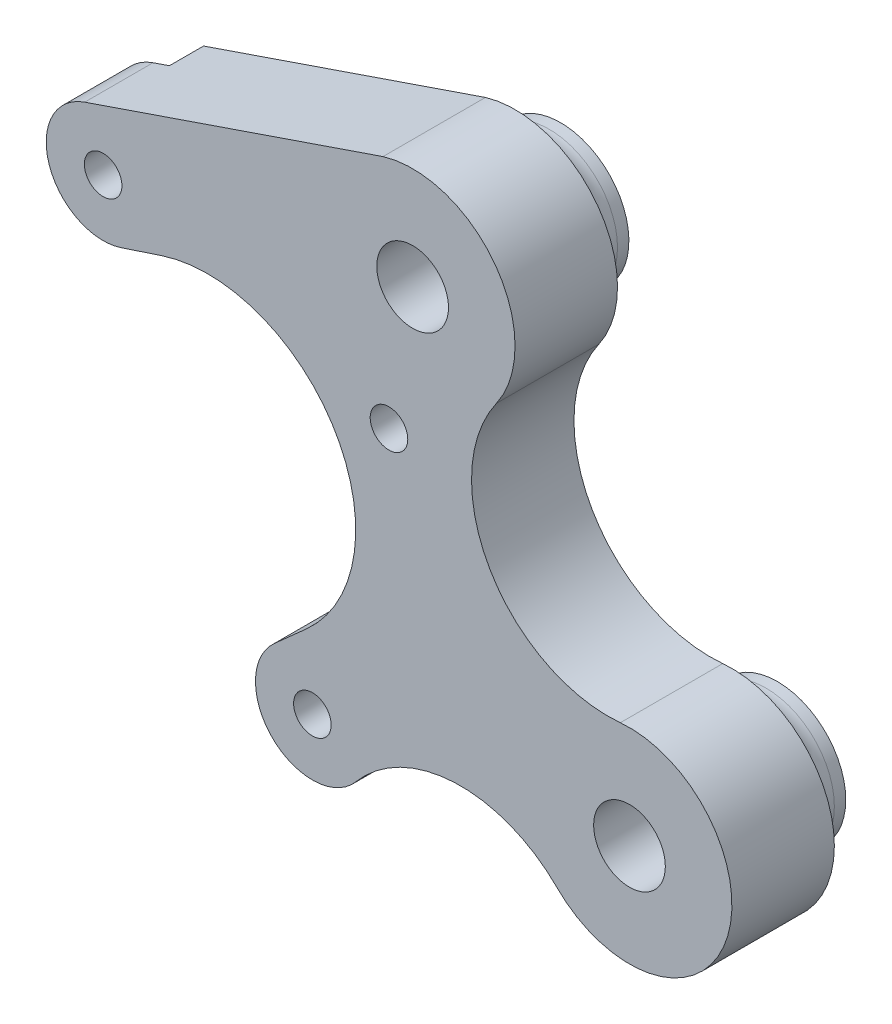
SolidWorks part; units mm, degrees
ref_plane "Front Plane" through (0, 0, 0) normal (0, 0, 1) x (1, 0, 0)
ref_plane "Top Plane" through (0, 0, 0) normal (0, 1, 0) x (1, 0, 0)
ref_plane "Right Plane" through (0, 0, 0) normal (1, 0, 0) x (0, 0, -1)
sketch "Sketch1" plane through (0, 0, 0) normal (0, 0, 1) x (1, 0, 0)
  line L0 (18, 21) -> (37.0525, -11.9999) construction
  line L1 (15.9217, 9.1924) -> (-9.1924, 15.9217) construction
  line L2 (-9.1924, 15.9217) -> (-15.9217, -9.1924) construction
  line L3 (-15.9217, -9.1924) -> (9.1924, -15.9217) construction
  line L4 (9.1924, -15.9217) -> (15.9217, 9.1924) construction
  line L5 (0, 0) -> (50.7667, 0) construction
  line L6 (0, 0) -> (-9.1924, 15.9217) construction
  line L7 (-4.0727, 12.3456) -> (-7.626, 11.1734)
  line L8 (8.6552, -9.6998) -> (5.8634, -12.191)
  line L9 (0, 0) -> (9.1924, -15.9217) construction
  line L10 (15.3981, 29.6157) -> (-10.8103, 20.6527)
  arc A0 (8.6552, -9.6998) -> (-4.0727, 12.3456) centre (0, 0) ccw
  circle A1 centre (18, 21) radius 3.15
  circle A2 centre (-9.1924, 15.9217) radius 1.65
  circle A3 centre (15.9217, 9.1924) radius 1.65
  circle A4 centre (9.1924, -15.9217) radius 1.65
  arc A5 (25.3607, 15.8211) -> (15.3981, 29.6157) centre (18, 21) ccw
  circle A6 centre (37.0525, -11.9999) radius 3.15
  arc A7 (-10.8103, 20.6527) -> (-7.626, 11.1734) centre (-9.1924, 15.9217) ccw
  arc A9 (30.6913, -18.3666) -> (36.2478, -3.0359) centre (37.0525, -11.9999) ccw
  arc A10 (5.8634, -12.191) -> (13.021, -19.1375) centre (9.1924, -15.9217) ccw
  arc A11 (30.6913, -18.3666) -> (13.021, -19.1375) centre (22.2097, -26.8556) ccw
  arc A12 (25.3607, 15.8211) -> (36.2478, -3.0359) centre (35.1749, 8.916) ccw
  dimension "D1" = 26
  dimension "D2" = 3.3
  dimension "D3" = 6.3
  dimension "D9" = 5
  dimension "D10" = 9
  dimension "D11" = 12
  dimension "D12" = 12
  dimension "D4" = 21
  dimension "D5" = 38.105
  dimension "D6" = 60
  dimension "D7" = 18
  dimension "D8" = 15
extrude "Boss-Extrude1" add sketch "Sketch1" along normal blind 9
sketch "Sketch2" plane through (0, 0, 0) normal (0, 0, -1) x (-1, 0, 0)
  line L0 (-9.1924, -15.9217) -> (-15.9217, 9.1924) construction
  line L1 (10.7961, 21.5278) -> (-20.1136, 13.2456)
  line L2 (-21.5278, 10.7961) -> (-13.2456, -20.1136)
  line L5 (-20.1136, 13.2456) -> (-21.5278, 10.7961)
  line L6 (23.2164, 14.3569) -> (10.7961, 21.5278)
  line L8 (-13.2456, -20.1136) -> (8.7791, -32.8295)
  line L9 (23.2164, 14.3569) -> (8.7791, -32.8295)
  line L11 (20.7057, -7.7281) -> (13.9247, 17.5792) [skipped]
  line L12 (-7.7281, -20.7057) -> (17.5792, -13.9247) [skipped]
  circle A0 centre (0, 0) radius 18 construction
  circle A1 centre (0, 0) radius 24.0416 construction
  circle A2 centre (-18, 21) radius 6 construction
  circle A3 centre (-18, 21) radius 3.15 construction
  point P2 (6.5153, 24.3153)
  point P3 (-22.0454, 12.7279)
  point P4 (-6.5153, -24.3153)
  point P5 (24.3153, -6.5153)
  dimension "D1" = 36
  dimension "D2" = 12
  dimension "D4" = 2
extrude "Cut-Extrude1" cut sketch "Sketch2" against normal offset from surface (3 mm away) 6 up to face at (21.15, 21, 9)
sketch "Sketch3" plane through (0, 0, 0) normal (0, 0, -1) x (-1, 0, 0)
  circle A0 centre (-18, 21) radius 6
  circle A1 centre (-18, 21) radius 3.15
  circle A2 centre (-37.0525, -11.9999) radius 3.15
  circle A3 centre (-37.0525, -11.9999) radius 6
  dimension "D1" = 12
extrude "Boss-Extrude2" add sketch "Sketch3" along normal blind 4
fillet "Fillet1" radius 3 2 edges at (24, 21, 0) (43.0525, -11.9999, 0)
